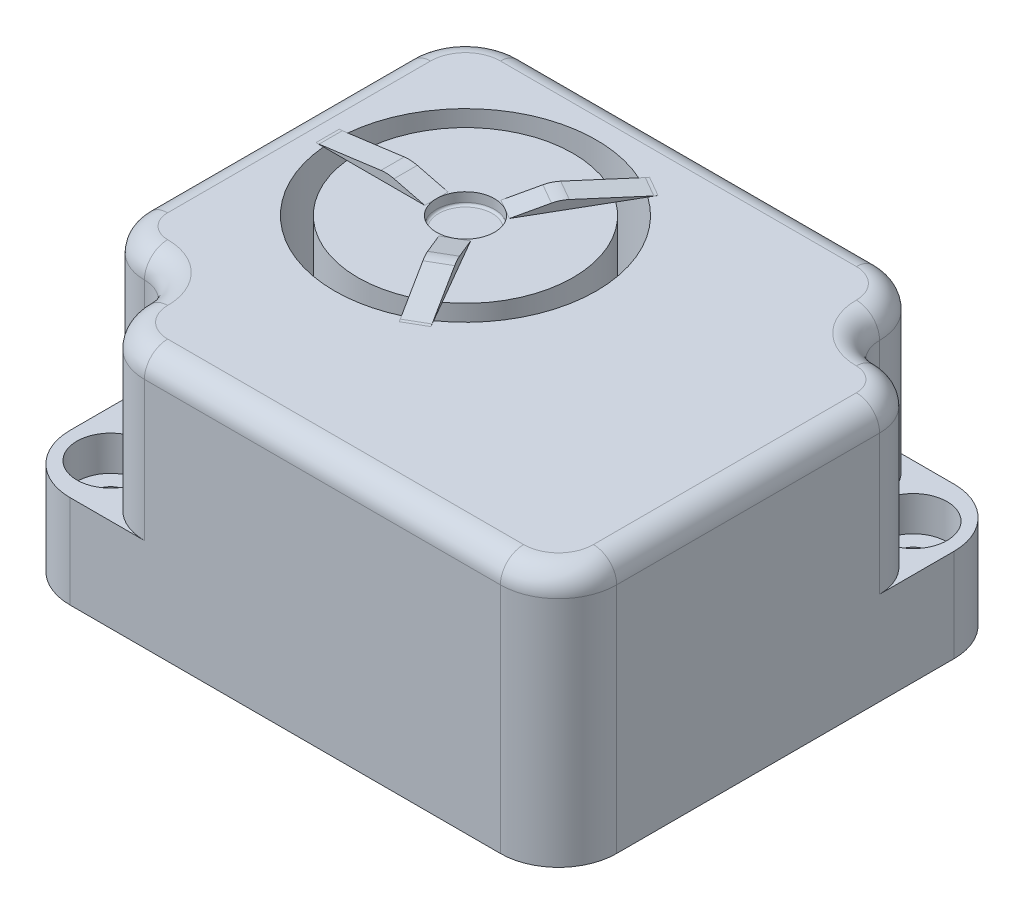
SolidWorks part; units mm, degrees
ref_plane "Plan de face" through (0, 0, 0) normal (0, 0, 1) x (1, 0, 0)
ref_plane "Plan de dessus" through (0, 0, 0) normal (0, 1, 0) x (1, 0, 0)
ref_plane "Plan de droite" through (0, 0, 0) normal (1, 0, 0) x (0, 0, -1)
sketch "Esquisse1" plane through (0, 0, 0) normal (0, 1, 0) x (1, 0, 0)
  line L1 (-23.5, -19.5) -> (23.5, -19.5)
  line L2 (-23.5, -19.5) -> (-23.5, 19.5)
  line L3 (-23.5, 19.5) -> (23.5, 19.5)
  line L4 (23.5, -19.5) -> (23.5, 19.5)
  line L5 (-23.5, -19.5) -> (23.5, 19.5) construction
  line L6 (-23.5, 19.5) -> (23.5, -19.5) construction
  point P0 (0, 0)
  dimension "D1" = 47
  dimension "D2" = 39
extrude "Boss.-Extru.1" add sketch "Esquisse1" along normal blind 22
hole_wizard "Chambrage pour vis à tête ronde bombée M31" positions "Esquisse3" profile "Esquisse4" counterbore size "M3" standard "ISO" end condition through all
sketch "Esquisse3" plane through (0, 22, 0) normal (0, 1, 0) x (1, 0, 0)
  line L0 (0, 8.3031) -> (0, 0) construction
  line L1 (0, 0) -> (11.7744, 0) construction
  point P0 (-19.5, -15)
  point P2 (19.5, 15)
  dimension "D1" = 30
  dimension "D2" = 39
  dimension "D3" = 19.5
  dimension "D4" = 15
sketch "Esquisse4" plane through (-19.5, 22, 15) normal (1, 0, 0) x (0, 0, 1)
  line L0 (0, 0) -> (0, 22)
  line L1 (0, 22) -> (1.5, 22)
  line L3 (1.5, 22) -> (1.5, 17)
  line L4 (1.5, 17) -> (2.9, 17)
  line L5 (2.9, 17) -> (2.9, 0)
  line L7 (2.9, 0) -> (0, 0)
  line L11 (0, -6.35) -> (0, 107.95) construction
  dimension "Diamètre du perçage jusqu'au prochain" = 3
  dimension "Profondeur du perçage jusqu'au prochain" = 22
  dimension "Diamètre du chambrage" = 5.8
  dimension "Profondeur du chambrage" = 17
sketch "Esquisse5" plane through (0, 22, 0) normal (0, 1, 0) x (1, 0, 0)
  line L0 (-23.5, 19.5) -> (-23.5, -19.5) construction
  line L1 (-23.5, -19.5) -> (23.5, -19.5) construction
  line L2 (-23.5, -8.1) -> (-23.5, -19.5)
  line L3 (-23.5, -19.5) -> (-12.1, -19.5)
  line L4 (-19.5, -9.6361) -> (-19.5, -15) construction
  line L5 (-19.5, -15) -> (-13.9251, -15) construction
  line L6 (23.5, 8.1) -> (23.5, 19.5)
  line L7 (23.5, 19.5) -> (12.1, 19.5)
  arc A0 (-23.5, -8.1) -> (-19.5, -12.1) centre (-19.5, -8.1) ccw
  arc A1 (-16.6, -15) -> (-12.1, -19.5) centre (-12.1, -15) ccw
  circle A2 centre (-19.5, -15) radius 2.9 construction
  arc A3 (-16.6, -15) -> (-19.5, -12.1) centre (-19.5, -15) ccw
  arc A4 (23.5, 8.1) -> (19.5, 12.1) centre (19.5, 8.1) ccw
  arc A5 (16.6, 15) -> (19.5, 12.1) centre (19.5, 15) ccw
  arc A6 (16.6, 15) -> (12.1, 19.5) centre (12.1, 15) ccw
  point P23 (0, 0)
  dimension "D1" = 2
extrude "Enlèv. mat.-Extru.1" cut sketch "Esquisse5" against normal offset from surface (14 mm away) 3 up to face at (-19.5, 5, 16.5)
fillet "Congé1" radius 5 4 edges at (23.5, 4, -19.5) (23.5, 11, 19.5) (-23.5, 4, 19.5) (-23.5, 11, -19.5)
fillet "Congé2" radius 2 12 edges at (-15.282, 22, 18.182) (-17.4494, 22, 12.9494) (-22.3284, 22, 10.9284) (-23.5, 22, -3.2) (-22.0355, 22, -18.0355) (-3.2, 22, -19.5) (15.282, 22, -18.182) (17.4494, 22, -12.9494) (22.3284, 22, -10.9284) (23.5, 22, 3.2) (22.0355, 22, 18.0355) (3.2, 22, 19.5)
sketch "Esquisse6" plane through (0, 22, 0) normal (0, 1, 0) x (1, 0, 0)
  circle A0 centre (-8.5, 4.5) radius 11.25
  circle A1 centre (-8.5, 4.5) radius 9.25
  dimension "D3" = 22.5
  dimension "D4" = 18.5
  dimension "D1" = 8.5
  dimension "D2" = 4.5
extrude "Enlèv. mat.-Extru.2" cut sketch "Esquisse6" against normal blind 15
sketch "Esquisse8" plane through (0, 22, 0) normal (0, 1, 0) x (1, 0, 0)
  circle A0 centre (-8.5, 4.5) radius 2.5
  circle A1 centre (-8.5, 4.5) radius 9.25 construction
  dimension "D1" = 5
extrude "Enlèv. mat.-Extru.3" cut sketch "Esquisse8" against normal blind 1
ref_point "Point1"
ref_plane "Plan1" through (0, 0, -4.5) normal (0, 0, 1) x (1, 0, 0)
sketch "Esquisse7" plane through (0, 0, -4.5) normal (0, 0, 1) x (1, 0, 0)
  line L0 (-20.2169, 22) -> (-11, 22)
  line L1 (-11, 22) -> (-13.6414, 22.661)
  line L2 (-14.7649, 22.7245) -> (-20.2169, 22)
  line L3 (-12.1, 22) -> (18.5, 22) construction
  arc A0 (-13.6414, 22.661) -> (-14.7649, 22.7245) centre (-14.3697, 19.7507) ccw
  point P11 (-14.1971, 22.8)
  dimension "D2" = 3
  dimension "D1" = 0.8
  dimension "D3" = 5.5
extrude "Boss.-Extru.5" add sketch "Esquisse7" along normal blind 1 and the other way blind 1 contours L2 L0 L1 A0
pattern_circular "Répétition circulaire1" count 3 over 360 about axis through (-8.5, 21, -4.5) along (0, 1, 0) of "Boss.-Extru.5"
fillet "Congé3" radius 2 3 edges at (-2.6415, 22, -14.6472) (-2.6415, 22, 5.6472) (-20.2169, 22, -4.5)
fillet "Congé4" radius 0.2 1 edges at (-8.5, 21, -2)
equation "\"D3@Esquisse3\"=\"D2@Esquisse3\"/2"
equation "\"D4@Esquisse3\"=\"D1@Esquisse3\"/2"
